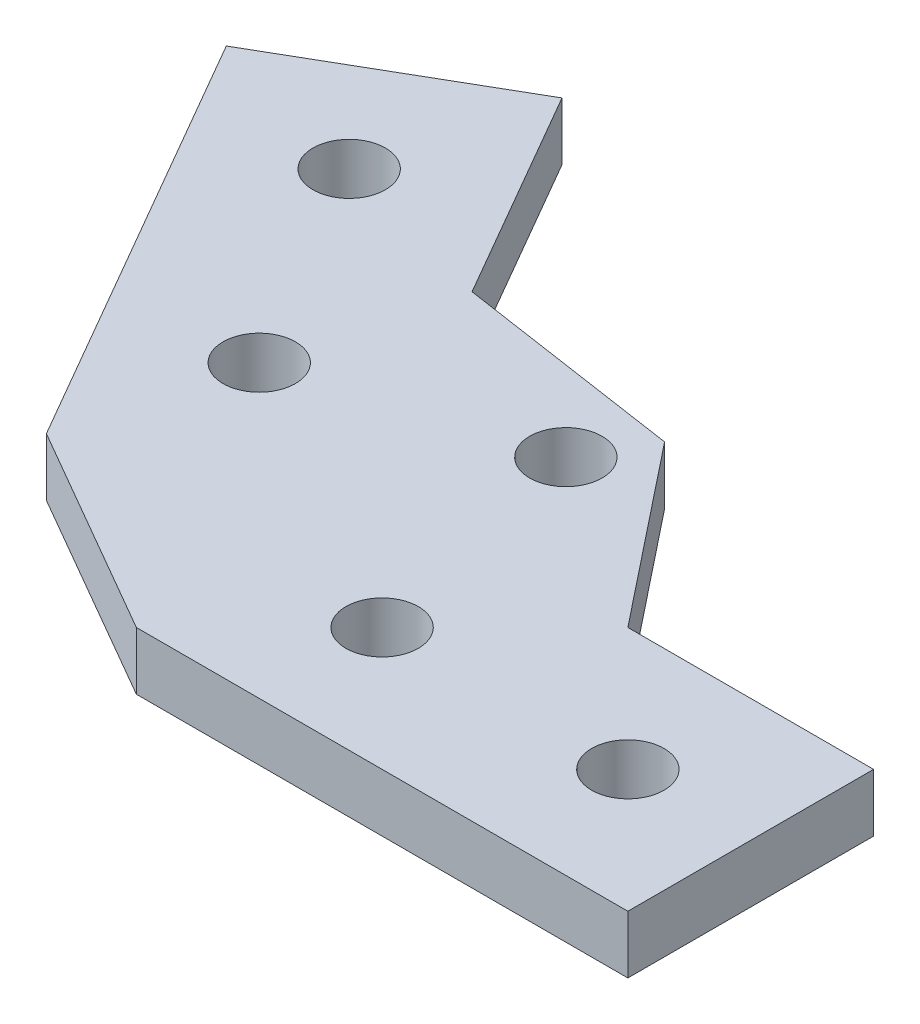
SolidWorks part; units mm, degrees
ref_plane "Front Plane" through (0, 0, 0) normal (0, 0, 1) x (1, 0, 0)
ref_plane "Top Plane" through (0, 0, 0) normal (0, 1, 0) x (1, 0, 0)
ref_plane "Right Plane" through (0, 0, 0) normal (1, 0, 0) x (0, 0, -1)
other "Configuration Table"
sketch "sketch1" plane through (0, 0, 0) normal (0, 1, 0) x (1, 0, 0)
  line L0 (0, -8.5) -> (8.5, -8.5) construction
  line L1 (0, 0) -> (34, 0)
  line L2 (0, 0) -> (0, -17)
  line L3 (0, -17) -> (34, -17)
  line L4 (34, 0) -> (34, -17)
  line L5 (8.5, -8.5) -> (25.5, -8.5) construction
  circle A1 centre (8.5, -8.5) radius 2.505
  circle A2 centre (25.5, -8.5) radius 2.505
  dimension "D4" = 5.01
  dimension "D1" = 17
  dimension "D2" = 34
  dimension "D3" = 8.5
  dimension "D6" = 17
  dimension "D5" = 2
extrude "Boss-Extrude1" add sketch "sketch1" along normal blind 4
sketch "Sketch9" plane through (0, 0, 0) normal (0, 1, 0) x (1, 0, 0)
  line L0 (0, 0) -> (34, 0) construction
  line L1 (0, 0) -> (17, 29.4449) construction
  dimension "D1" = 60
ref_plane "Plane2" through (0, 0, 0) normal (-0.866, 0, -0.5) x (-0.5, 0, 0.866)
mirror "Mirror6" about plane through (0, 0, 0) normal (-0.866, 0, -0.5) of bodies 102 110
sketch "Sketch11" plane through (0, 0, 0) normal (0, 1, 0) x (1, 0, 0)
  line L0 (-14.7224, -8.5) -> (0, -17)
  line L1 (0, 0) -> (-14.7224, -8.5) construction
  line L2 (0, 0) -> (0, -17) construction
  line L3 (0, 0) -> (-14.7224, -8.5)
  line L4 (0, 0) -> (0, -17)
extrude "Boss-Extrude2" add sketch "Sketch11" along normal blind 4
sketch "Sketch13" plane through (0, 0, 0) normal (0, 1, 0) x (1, 0, 0)
  line L0 (-11.6112, 3.1112) -> (4.6528, 8.059) construction
  line L1 (0, 0) -> (17, 29.4449) construction
  line L2 (4.6528, 8.059) -> (8.5, -8.5) construction
  line L4 (7.1528, 12.3891) -> (-8.5, 14.7224)
  line L5 (-17, 29.4449) -> (0, 0) construction
  line L6 (7.1528, 12.3891) -> (17, 0)
  line L7 (0, 0) -> (34, 0) construction
  line L8 (0, 0) -> (17, 29.4449) construction
  line L9 (-8.5, 14.7224) -> (0, 0)
  line L10 (0, 0) -> (17, 0)
  circle A0 centre (8.5, -8.5) radius 2.505 construction
  circle A1 centre (-11.6112, 3.1112) radius 2.505 construction
  circle A2 centre (8.5, -8.5) radius 2.505 construction
  circle A3 centre (-11.6112, 3.1112) radius 2.505 construction
  circle A4 centre (4.6528, 8.059) radius 2.505
  dimension "D1" = 17
  dimension "D2" = 5.01
  dimension "D3" = 5
  dimension "D4" = 17
extrude "Boss-Extrude3" add sketch "Sketch13" along normal blind 4
equation "\"D2@sketch1\" = \"length\""
equation "\"holes\"= 2'Holes per side"
equation "\"cdist\"= 17mm'centre distance between holes"
equation "\"width\"= 17mm"
equation "\"length\"= \"cdist\" * \"holes\""
equation "\"D1@sketch1\"=\"width\""
equation "\"hdiam\"= 5.01mm'Hole diametre"
equation "\"D4@sketch1\" = \"hdiam\""
equation "\"D6@sketch1\" = \"cdist\""
equation "\"D5@sketch1\" = \"holes\""
equation "\"D1@Boss-Extrude1\"=\"supportheight\""
equation "\"joint\"= 120"
equation "\"D1@Sketch9\"=\"joint\"/2"
equation "\"D1@Boss-Extrude2\"=\"supportheight\""
equation "\"D2@Sketch13\"=\"hdiam\""
equation "\"D4@Sketch13\"=\"cdist\""
equation "\"D1@Boss-Extrude3\"=\"supportheight\""
equation "\"supportheight\"= 4mm"
equation "\"tolerance\"= 0.04mm"
equation "\"insetwidth\"= 7mm"
